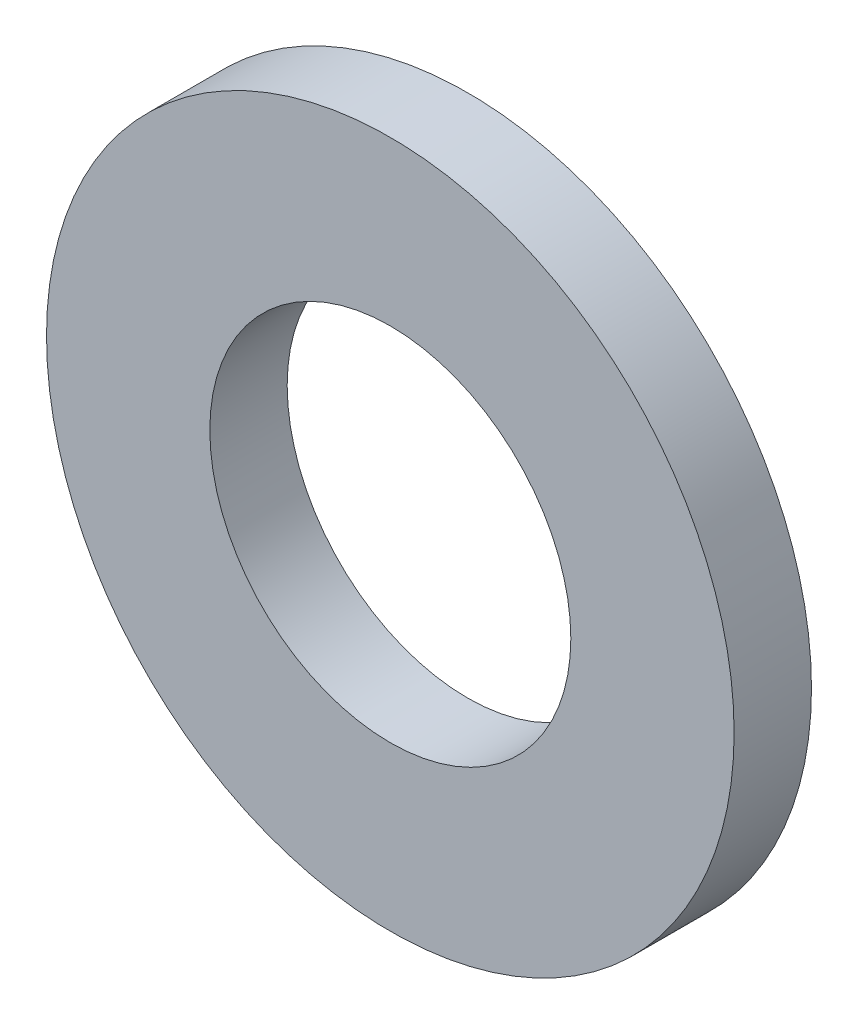
SolidWorks part; units mm, degrees
material "AISI 1045 Steel, cold drawn"
ref_plane "Front Plane" through (0, 0, 0) normal (0, 0, 1) x (1, 0, 0)
ref_plane "Top Plane" through (0, 0, 0) normal (0, 1, 0) x (1, 0, 0)
ref_plane "Right Plane" through (0, 0, 0) normal (1, 0, 0) x (0, 0, -1)
sketch "Sketch1" plane through (0, 0, 0) normal (0, 0, 1) x (1, 0, 0)
  circle A0 centre (0, 0) radius 8
  circle A1 centre (0, 0) radius 4.2
  dimension "OD" = 16
  dimension "ID1" = 8.4
extrude "washer_boss" add sketch "Sketch1" along normal blind 1.8
ref_axis "washer" through (0, 0, -0.09) along (0, 0, 1)
